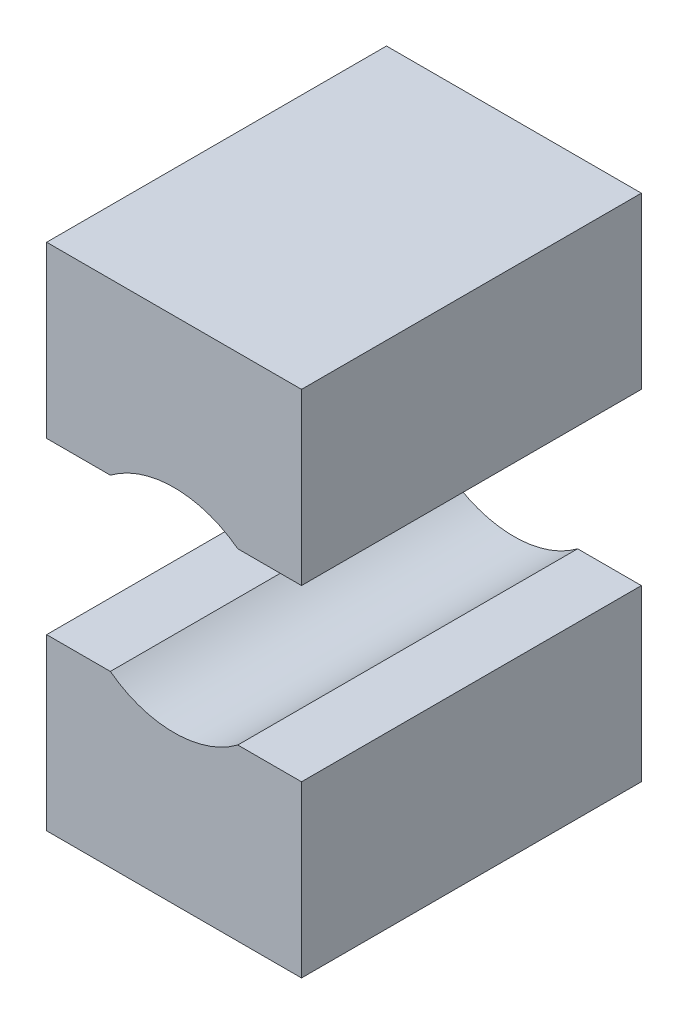
SolidWorks part; units mm, degrees
ref_plane "Vorne" through (0, 0, 0) normal (0, 0, 1) x (1, 0, 0)
ref_plane "Oben" through (0, 0, 0) normal (0, 1, 0) x (1, 0, 0)
ref_plane "Rechts" through (0, 0, 0) normal (1, 0, 0) x (0, 0, -1)
sketch "Skizze1" plane through (0, 0, 0) normal (0, 0, 1) x (1, 0, 0)
  line L1 (-15, 30) -> (15, 30)
  line L2 (-15, 30) -> (-15, 10)
  line L3 (-15, 10) -> (15, 10)
  line L4 (15, 30) -> (15, 10)
  line L5 (-15, 30) -> (15, 10) construction
  line L6 (-15, 10) -> (15, 30) construction
  line L7 (-15, -10) -> (15, -10)
  line L8 (-15, -10) -> (-15, -30)
  line L9 (-15, -30) -> (15, -30)
  line L10 (15, -10) -> (15, -30)
  line L11 (-15, -10) -> (15, -30) construction
  line L12 (-15, -30) -> (15, -10) construction
  point P0 (0, 20)
  point P5 (0, -20)
  dimension "D1" = 10
  dimension "D2" = 20
  dimension "D3" = 20
  dimension "D4" = 20
  dimension "D5" = 30
  dimension "D6" = 15
  dimension "D7" = 15
  dimension "D8" = 30
extrude "Aufsatz-Linear austragen1" add sketch "Skizze1" against normal blind 40
sketch "Skizze2" plane through (0, 0, 0) normal (0, 0, 1) x (1, 0, 0)
  circle A0 centre (0, 0) radius 12.5
  dimension "D1" = 25
extrude "Schnitt-Linear austragen1" cut sketch "Skizze2" against normal blind 50
ref_axis "Achse1" through (0, 0, -80.9) along (0, 0, 1)
